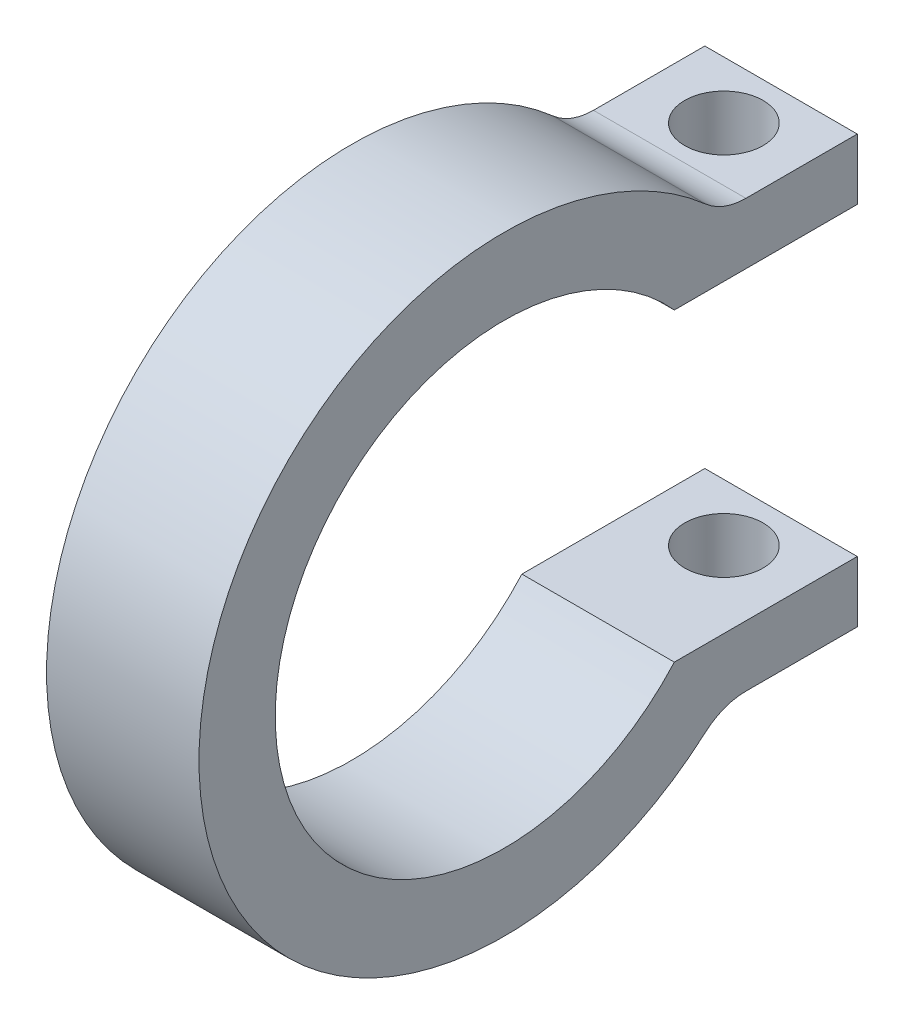
SolidWorks part; units mm, degrees
material "6061-T6 (SS)"
ref_plane "Front Plane" through (0, 0, 0) normal (1, 0, 0) x (0, 1, 0)
ref_plane "Top Plane" through (0, 0, 0) normal (0, 0, 1) x (0, 1, 0)
ref_plane "Right Plane" through (0, 0, 0) normal (0, 1, 0) x (-1, 0, 0)
sketch "Sketch2" plane through (0, 0, 0) normal (1, 0, 0) x (0, 1, 0)
  line L0 (-6.35, -7.0995) -> (6.35, -7.0995) construction
  line L1 (-6.35, -7.0995) -> (-6.35, -14.7195)
  line L2 (6.35, -7.0995) -> (6.35, -14.7195)
  line L3 (-8.89, -9.0696) -> (-8.89, -14.7195)
  line L4 (-8.89, -14.7195) -> (-6.35, -14.7195)
  line L5 (6.35, -14.7195) -> (8.89, -14.7195)
  line L6 (8.89, -14.7195) -> (8.89, -9.0696)
  line L7 (-3.175, -8.9803) -> (3.175, -8.9803) construction
  arc A0 (6.35, -7.0995) -> (-6.35, -7.0995) centre (0, 0) ccw
  arc A1 (8.89, -9.0696) -> (-8.89, -9.0696) centre (0, 0) ccw
  circle A2 centre (0, 0) radius 9.525 construction
  dimension "D2" = 9.525
  dimension "D4" = 12.7
  dimension "D1" = 12.7
  dimension "D3" = 7.62
  dimension "D5" = 2.54
  dimension "D6" = 2.54
  dimension "D7" = 6.35
  dimension "D8" = 5.7393
extrude "Boss-Extrude1" add sketch "Sketch2" along normal blind 6.35
sketch "Sketch3" plane through (0, -8.89, 0) normal (0, -1, 0) x (1, 0, 0)
  line L1 (3.175, -9.0696) -> (3.175, -14.7195) construction
  line L2 (6.35, -9.0696) -> (0, -9.0696) construction
  line L3 (6.35, -14.7195) -> (0, -14.7195) construction
  point P9 (3.175, -12.3383)
  dimension "D1" = 2.3813
hole_wizard "#4 Clearance Hole1" positions "Sketch3" profile "Sketch4" hole size "#4" standard "ANSI Inch" end condition through all
sketch "Sketch4" plane through (3.175, -8.89, -12.3383) normal (1, 0, 0) x (0, 0, -1)
  line L0 (0, 0) -> (0, 21.59)
  line L1 (0, 21.59) -> (1.6319, 21.59)
  line L2 (1.6319, 21.59) -> (1.6319, 0)
  line L5 (1.6319, 0) -> (0, 0)
  line L11 (0, -6.35) -> (0, 107.95) construction
  dimension "Thru Hole Dia." = 3.2639
  dimension "Thru Hole Depth" = 21.59
fillet "Fillet2" radius 2.54 2 edges at (3.175, 8.89, -9.0696) (3.175, -8.89, -9.0696)
